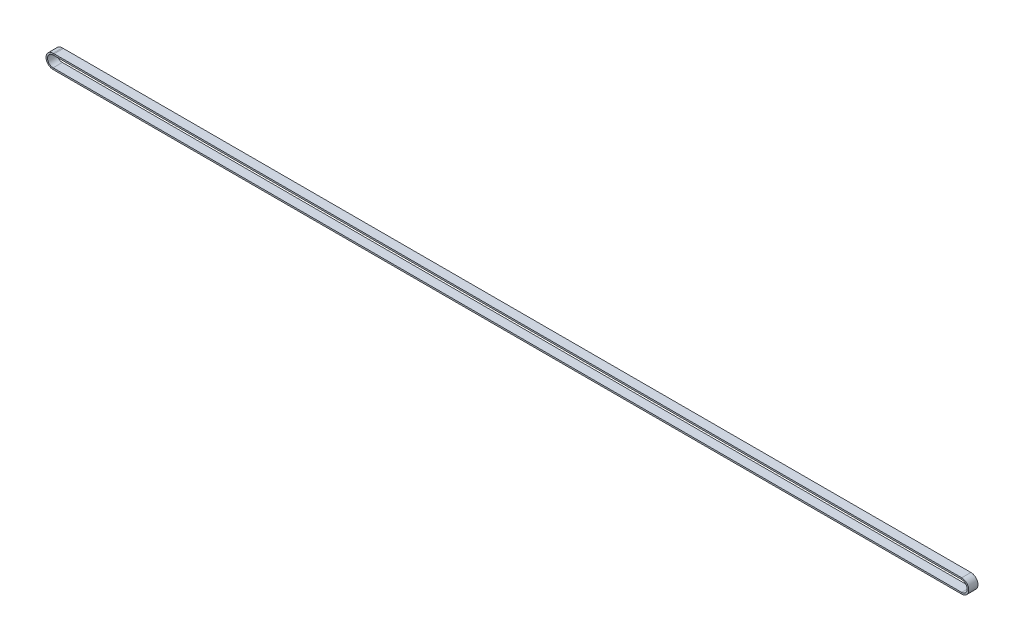
SolidWorks part; units mm, degrees
ref_plane "Front Plane" through (0, 0, 0) normal (0, 0, 1) x (1, 0, 0)
ref_plane "Top Plane" through (0, 0, 0) normal (0, 1, 0) x (1, 0, 0)
ref_plane "Right Plane" through (0, 0, 0) normal (1, 0, 0) x (0, 0, -1)
sketch "Sketch2" plane through (0, 0, -62.4834) normal (0, 0, 1) x (1, 0, 0)
  line L0 (0, 0) -> (1, 0) construction
  line L1 (0, 0) -> (0, 1) construction
  line L2 (-1, -249.662) -> (883.5206, -249.662)
  line L3 (883.5206, -263.462) -> (-1, -263.462)
  arc A0 (-1, -263.462) -> (-1, -249.662) centre (-1, -256.562) cw
  arc A1 (883.5206, -249.662) -> (883.5206, -263.462) centre (883.5206, -256.562) cw
sketch "Sketch3" plane through (0, 0, 0) normal (1, 0, 0) x (0, 0, -1)
  line L1 (62.4834, -251.162) -> (53.4834, -251.162)
  line L2 (62.4834, -251.162) -> (62.4834, -249.662)
  line L3 (62.4834, -249.662) -> (53.4834, -249.662)
  line L4 (53.4834, -251.162) -> (53.4834, -249.662)
  dimension "D1" = 9
  dimension "D2" = 1.5
sweep "Sweep1" add profiles "Sketch3" path "Sketch2"
